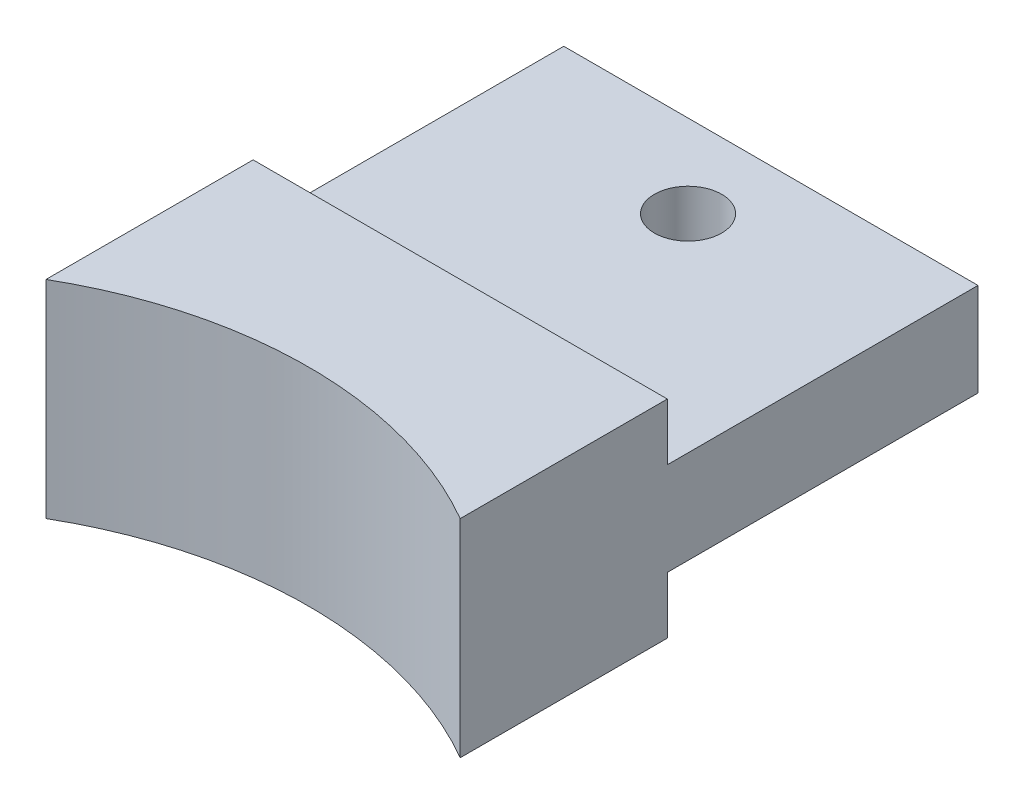
SolidWorks part; units mm, degrees
ref_plane "Front Plane" through (0, 0, 0) normal (0, 0, 1) x (1, 0, 0)
ref_plane "Top Plane" through (0, 0, 0) normal (0, 1, 0) x (1, 0, 0)
ref_plane "Right Plane" through (0, 0, 0) normal (1, 0, 0) x (0, 0, -1)
sketch "Sketch1" plane through (0, 0, 0) normal (0, 0, 1) x (1, 0, 0)
  line L1 (-10, -5) -> (10, -5)
  line L2 (-10, -5) -> (-10, 5)
  line L3 (-10, 5) -> (10, 5)
  line L4 (10, -5) -> (10, 5)
  line L5 (-10, -5) -> (10, 5) construction
  line L6 (-10, 5) -> (10, -5) construction
  point P0 (0, 0)
  dimension "D1" = 10
  dimension "D2" = 20
extrude "Boss-Extrude1" add sketch "Sketch1" along normal blind 10
sketch "Sketch2" plane through (0, 5, 0) normal (0, 1, 0) x (1, 0, 0)
  line L0 (-10, -10) -> (10, -10)
  arc A0 (-10, -10) -> (10, -10) centre (0, -27.3205) cw
  dimension "D1" = 20
extrude "Cut-Extrude1" cut sketch "Sketch2" against normal up to surface (10 mm away) up to face at (0, -5, 5)
sketch "Sketch3" plane through (0, 0, 0) normal (0, 0, -1) x (-1, 0, 0)
  line L0 (10, 5) -> (10, -5) construction
  line L1 (-10, -2.25) -> (10, -2.25)
  line L2 (-10, -2.25) -> (-10, 2.25)
  line L3 (-10, 2.25) -> (10, 2.25)
  line L4 (10, -2.25) -> (10, 2.25)
  line L5 (-10, -2.25) -> (10, 2.25) construction
  line L6 (-10, 2.25) -> (10, -2.25) construction
  point P0 (0, 0)
  dimension "D1" = 4.5
extrude "Boss-Extrude2" add sketch "Sketch3" along normal blind 15 contours L3 L4 L1 L2
hole_wizard "Tap Drill for M3x0.5 Tap6" positions "Sketch18" profile "Sketch19" hole size "M3x0.5" standard "ANSI Metric" end condition up to next
sketch "Sketch18" plane through (0, 2.25, 0) normal (0, 1, 0) x (1, 0, 0)
  line L2 (10, 15) -> (-10, 15) construction
  point P0 (0, 11)
  dimension "D1" = 4
sketch "Sketch19" plane through (0, 2.25, -11) normal (1, 0, 0) x (0, 0, 1)
  line L0 (0, 0) -> (0, 4.5)
  line L1 (0, 4.5) -> (1.625, 4.5)
  line L2 (1.625, 4.5) -> (1.625, 0)
  line L5 (1.625, 0) -> (0, 0)
  line L11 (0, -6.35) -> (0, 107.95) construction
  dimension "Thru Hole Dia." = 3.25
  dimension "Thru Hole Depth" = 4.5
